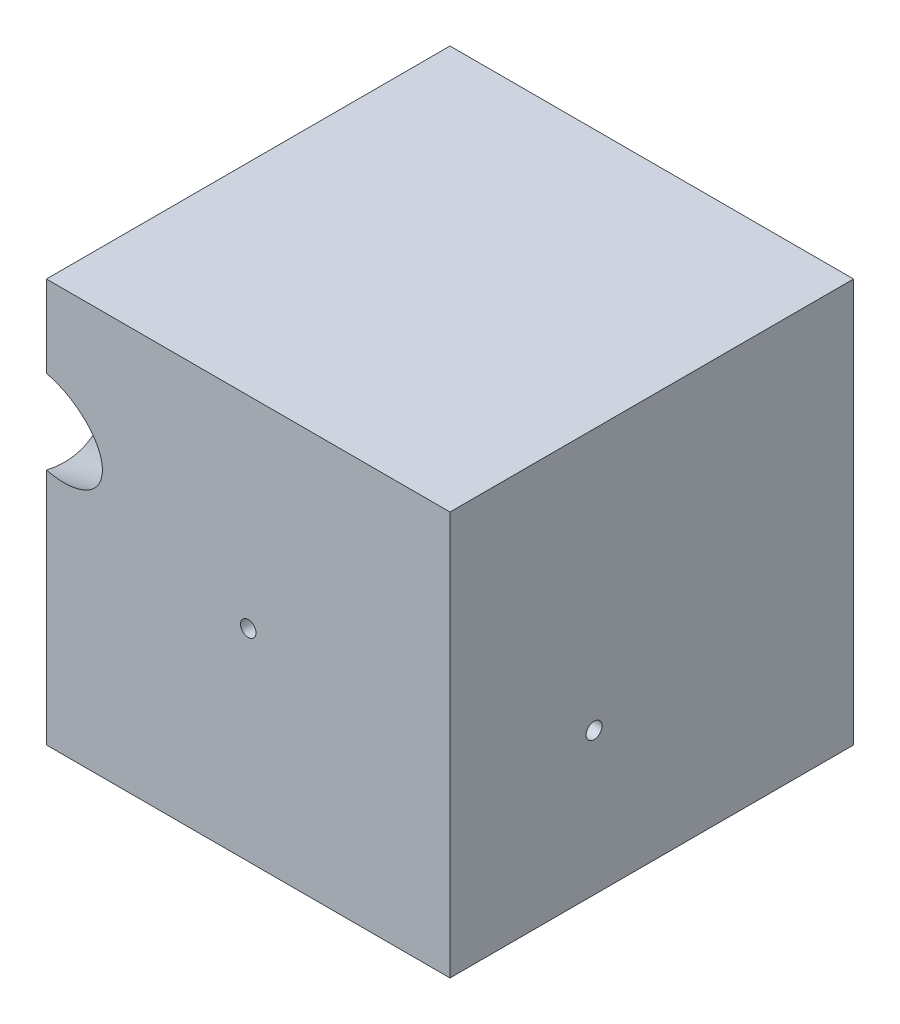
SolidWorks part; units mm, degrees
other "Markup1"
sketch "Sketch17" plane through (26, 26, 0) normal (0.2144, 0.2359, -0.9478) x (-0.9746, -0.0125, -0.2235)
other "Markup2"
sketch "Sketch18" plane through (26, 26, 52) normal (0.7408, 0.3225, 0.5893) x (0.4554, 0.4038, -0.7934)
other "Markup3"
sketch "Sketch19" plane through (-26, 26, 52) normal (-0.3816, 0.4867, 0.7858) x (0.9196, 0.2861, 0.2694)
material "ABS"
ref_plane "Front Plane" through (0, 0, 0) normal (0, 0, 1) x (1, 0, 0)
ref_plane "Top Plane" through (0, 0, 0) normal (0, 1, 0) x (1, 0, 0)
ref_plane "Right Plane" through (0, 0, 0) normal (1, 0, 0) x (0, 0, -1)
sketch "Square" plane through (0, 0, 0) normal (0, 0, 1) x (1, 0, 0)
  line L1 (-26, -26) -> (26, -26)
  line L2 (-26, -26) -> (-26, 26)
  line L3 (-26, 26) -> (26, 26)
  line L4 (26, -26) -> (26, 26)
  line L5 (-26, -26) -> (26, 26) construction
  line L6 (-26, 26) -> (26, -26) construction
  point P0 (0, 0)
  dimension "D1" = 52
extrude "Cube-Extrusion" add sketch "Square" along normal blind 52
ref_plane "StickPlane" through (-28.8889, 14.4444, 28.8889) normal (0.6667, -0.3333, -0.6667) x (-0.7454, -0.2981, -0.5963)
sketch "Stick-Hole" plane through (-28.8889, 14.4444, 28.8889) normal (0.6667, -0.3333, -0.6667) x (-0.7454, -0.2981, -0.5963)
  line L0 (-19.3793, 0) -> (-3.8759, -46.5102) construction
  circle A0 centre (-14.6358, -14.2302) radius 5.1
  dimension "D2" = 10.2
  dimension "D1" = 15
extrude "Stick-Cut" cut sketch "Stick-Hole" against normal through all from offset 15
sketch "Sketch12" plane through (0, 0, 52) normal (0, 0, 1) x (1, 0, 0)
  circle A0 centre (0, 0) radius 1
  point P3 (0, 0)
  dimension "D1" = 2
extrude "Cut-Extrude8" cut sketch "Sketch12" against normal blind 12
sketch "Sketch13" plane through (0, 0, 0) normal (0, 0, -1) x (-1, 0, 0)
  circle A0 centre (0, 0) radius 1
  point P3 (0, 0)
  dimension "D1" = 2
extrude "Cut-Extrude9" cut sketch "Sketch13" against normal blind 12
sketch "Sketch14" plane through (-26, 0, 0) normal (-1, 0, 0) x (0, 0, 1)
  line L0 (0, 26) -> (0, -26) construction
  line L1 (52, 26) -> (0, 26) construction
  line L2 (52, -26) -> (0, -26) construction
  circle A0 centre (10.5144, 15.4825) radius 1
  circle A1 centre (20.4493, -13.8146) radius 1
  dimension "D1" = 2
  dimension "D2" = 10.5144
  dimension "D3" = 10.5175
  dimension "D4" = 20.4493
  dimension "D5" = 12.1854
extrude "Cut-Extrude10" cut sketch "Sketch14" against normal blind 12
sketch "Sketch15" plane through (26, 0, 0) normal (1, 0, 0) x (0, 0, -1)
  circle A0 centre (-33.4399, -7.6506) radius 1.0307
  point P2 (0, 0)
extrude "Cut-Extrude11" cut sketch "Sketch15" against normal blind 12
sketch "Sketch16" plane through (0, -26, 0) normal (0, -1, 0) x (1, 0, 0)
  line L0 (-26, 52) -> (-26, 0) construction
  line L1 (-26, 0) -> (26, 0) construction
  circle A0 centre (-9, 44.28) radius 1
  dimension "D3" = 2
  dimension "D1" = 17
  dimension "D2" = 44.28
extrude "Cut-Extrude12" cut sketch "Sketch16" against normal blind 12
ref_plane "Plane1" through (0, 0, 0) normal (0.2823, 0.9593, 0) x (0.9593, -0.2823, 0)
